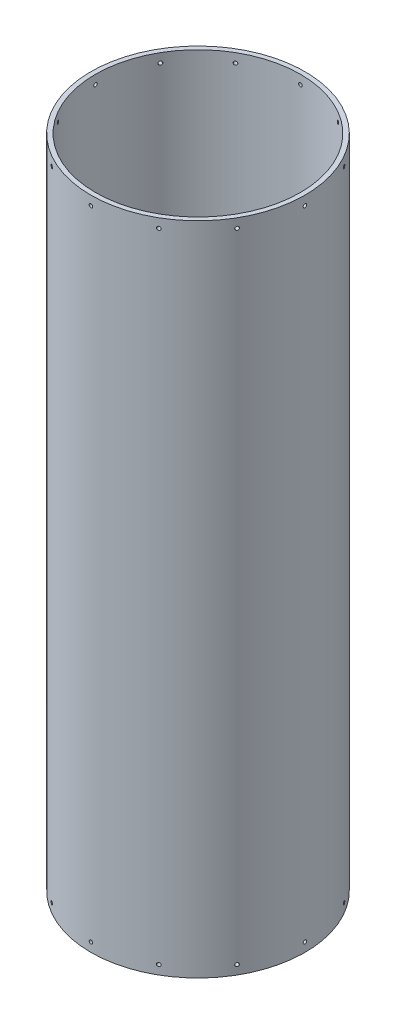
SolidWorks part; units mm, degrees
material "6061-T6 (SS)"
ref_plane "Front Plane" through (0, 0, 0) normal (0, 0, 1) x (1, 0, 0)
ref_plane "Top Plane" through (0, 0, 0) normal (0, 1, 0) x (1, 0, 0)
ref_plane "Right Plane" through (0, 0, 0) normal (1, 0, 0) x (0, 0, -1)
sketch "Sketch1" plane through (0, 0, 0) normal (0, 1, 0) x (1, 0, 0)
  circle A0 centre (0, 0) radius 142.875
  circle A1 centre (0, 0) radius 149.225
  dimension "D1" = 285.75
  dimension "D2" = 298.45
extrude "Boss-Extrude1" add sketch "Sketch1" along normal blind 914.4
ref_plane "Plane1" through (149.225, 0, 0) normal (1, 0, 0) x (0, 0, -1)
hole_wizard "#10 (0.1935) Diameter Hole1" positions "Sketch2" profile "Sketch4" hole size "#10" standard "ANSI Inch" end condition up to next
sketch "Sketch2" plane through (149.225, 0, 0) normal (1, 0, 0) x (0, 0, -1)
  line L0 (149.225, 914.4) -> (-149.225, 914.4) construction
  line L1 (0, 164.1475) -> (0, -164.1475) construction
  point P0 (0, 901.7)
  dimension "D1" = 12.7
sketch "Sketch4" plane through (149.225, 901.7, 0) normal (0, 1, 0) x (0, 0, -1)
  line L0 (0, 0) -> (0, 344.3972)
  line L1 (0, 344.3972) -> (2.4574, 344.3972)
  line L2 (2.4574, 344.3972) -> (2.4574, 0)
  line L5 (2.4574, 0) -> (0, 0)
  line L11 (0, -6.35) -> (0, 107.95) construction
  dimension "Thru Hole Dia." = 4.9149
  dimension "Thru Hole Depth" = 344.3972
pattern_circular "CirPattern1" count 12 over 360 about axis through (0, 914.4, 0) along (0, 1, 0) of "#10 (0.1935) Diameter Hole1"
ref_plane "Plane2" through (0, 457.2, 0) normal (0, -1, 0) x (-1, 0, 0)
mirror "Mirror1" about plane through (0, 457.2, 0) normal (0, -1, 0) of "CirPattern1"
